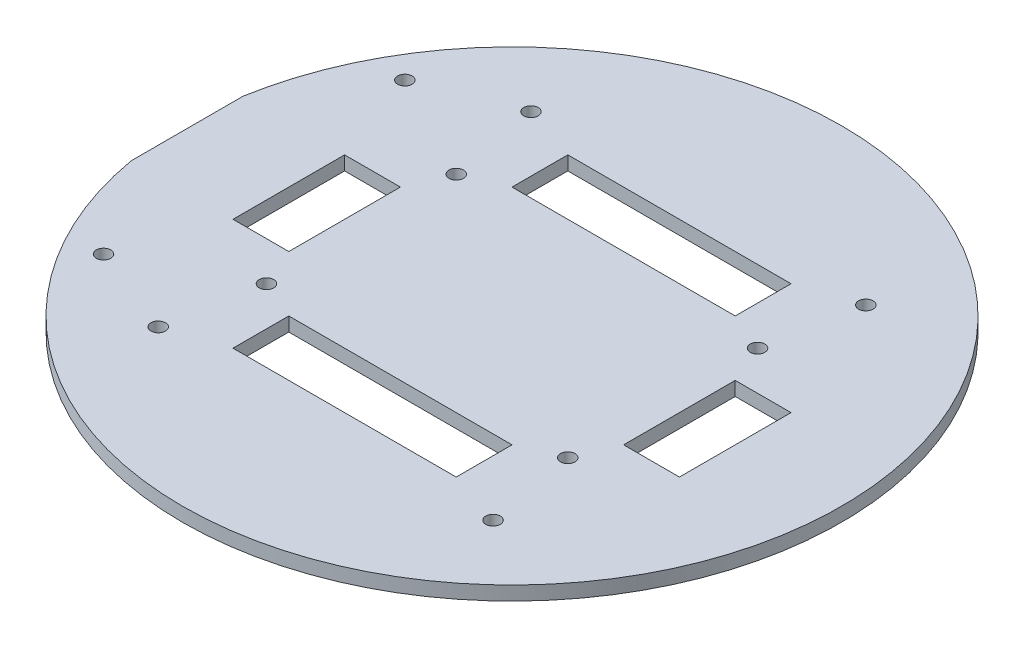
SolidWorks part; units mm, degrees
material "Acrylic (Medium-high impact)"
ref_plane "Front Plane" through (0, 0, 0) normal (0, 0, 1) x (1, 0, 0)
ref_plane "Top Plane" through (0, 0, 0) normal (0, 1, 0) x (1, 0, 0)
ref_plane "Right Plane" through (0, 0, 0) normal (1, 0, 0) x (0, 0, -1)
sketch "Sketch1" plane through (0, 0, 0) normal (0, 1, 0) x (1, 0, 0)
  line L0 (-73.9169, 12.7) -> (-73.9169, -12.7)
  line L1 (-73.9169, 12.7) -> (-73.9169, -12.7) construction
  line L2 (-34.29, 21.59) -> (34.29, 21.59) construction
  line L3 (34.29, 21.59) -> (34.29, -21.59) construction
  line L4 (34.29, -21.59) -> (-34.29, -21.59) construction
  line L5 (-34.29, -21.59) -> (-34.29, 21.59) construction
  line L6 (0, 21.59) -> (0, 75) construction
  line L7 (34.29, 0) -> (75, 0) construction
  line L8 (0, -25.4) -> (0, -21.59) construction
  line L9 (-34.29, 0) -> (-38.1, 0) construction
  line L10 (-25.4, 38.1) -> (25.4, 38.1)
  line L11 (-25.4, 38.1) -> (-25.4, 25.4)
  line L12 (-25.4, 25.4) -> (25.4, 25.4)
  line L13 (25.4, 38.1) -> (25.4, 25.4)
  line L14 (38.1, 12.7) -> (50.8, 12.7)
  line L15 (38.1, 12.7) -> (38.1, -12.7)
  line L16 (38.1, -12.7) -> (50.8, -12.7)
  line L17 (50.8, 12.7) -> (50.8, -12.7)
  line L18 (25.4, -25.4) -> (-25.4, -25.4)
  line L19 (25.4, -25.4) -> (25.4, -38.1)
  line L20 (25.4, -38.1) -> (-25.4, -38.1)
  line L21 (-25.4, -25.4) -> (-25.4, -38.1)
  line L22 (-50.8, -12.7) -> (-38.1, -12.7)
  line L23 (-50.8, -12.7) -> (-50.8, 12.7)
  line L24 (-50.8, 12.7) -> (-38.1, 12.7)
  line L25 (-38.1, -12.7) -> (-38.1, 12.7)
  line L26 (38.1, 12.7) -> (34.29, 12.7) construction
  line L27 (25.4, 25.4) -> (25.4, 21.59) construction
  arc A0 (-73.9169, -12.7) -> (-73.9169, 12.7) centre (0, 0) ccw
  arc A1 (55.356, -50.6035) -> (55.356, 50.6035) centre (0, 0) ccw construction
  circle A2 centre (-34.29, 21.59) radius 1.651
  circle A3 centre (34.29, 21.59) radius 1.651
  circle A4 centre (-34.29, -21.59) radius 1.651
  circle A5 centre (34.29, -21.59) radius 1.651
  circle A6 centre (-38.1, 42.418) radius 1.651 construction
  circle A7 centre (38.1, -42.418) radius 1.651
  circle A8 centre (-38.1, -42.418) radius 1.651
  circle A9 centre (-58.6769, -34.29) radius 1.651
  circle A10 centre (-58.6769, 34.29) radius 1.651
  circle A11 centre (-38.1, 42.418) radius 1.651
  circle A12 centre (38.1, 42.418) radius 1.651
  circle A13 centre (38.1, -42.418) radius 1.651 construction
  dimension "D1" = 68.58
  dimension "D2" = 43.18
  dimension "D3" = 3.81
  dimension "D4" = 12.7
  dimension "D5" = 50.8
  dimension "D6" = 25.4
extrude "Boss-Extrude1" add sketch "Sketch1" along normal blind 3.175
